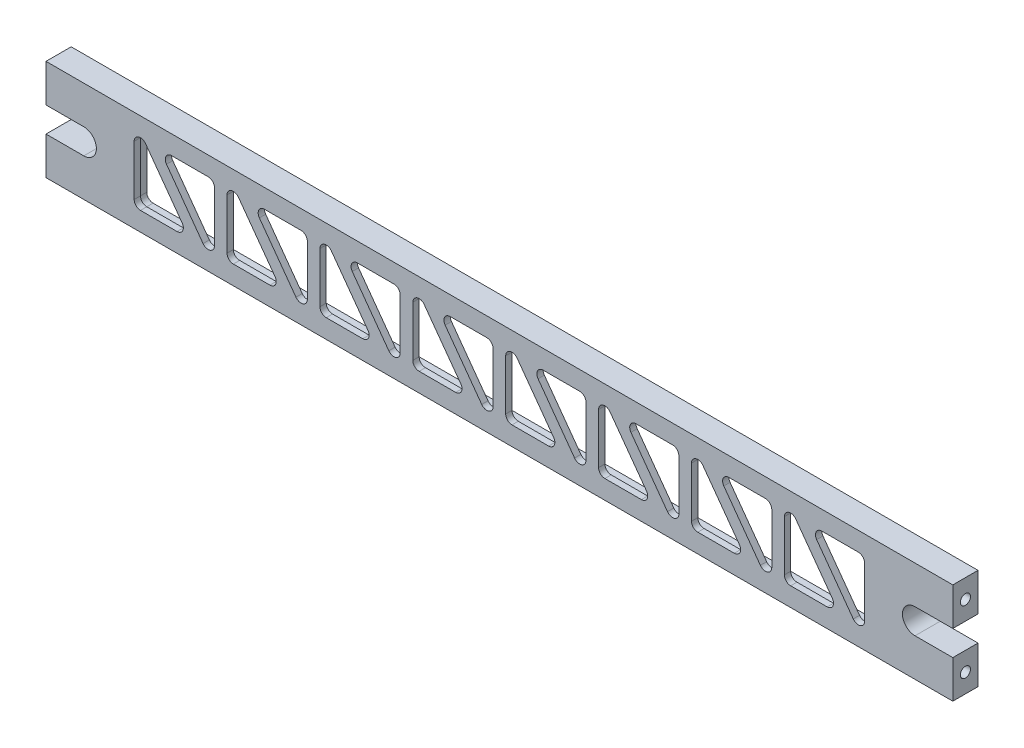
SolidWorks part; units mm, degrees
material "6061 Alloy"
ref_plane "Front Plane" through (0, 0, 0) normal (0, 0, 1) x (1, 0, 0)
ref_plane "Top Plane" through (0, 0, 0) normal (0, 1, 0) x (1, 0, 0)
ref_plane "Right Plane" through (0, 0, 0) normal (1, 0, 0) x (0, 0, -1)
sketch "Sketch1" plane through (0, 0, 0) normal (1, 0, 0) x (0, 0, -1)
  line L1 (0, 0) -> (12.7, 0)
  line L2 (0, 0) -> (0, 50.8)
  line L3 (0, 50.8) -> (12.7, 50.8)
  line L4 (12.7, 0) -> (12.7, 50.8)
  dimension "D1" = 12.7
  dimension "D2" = 50.8
extrude "Boss-Extrude1" add sketch "Sketch1" along normal mid plane 457.2
hole_wizard "1/4-20 Tapped Hole1" positions "3DSketch1" profile "Sketch2" tap size "1/4-20" standard "ANSI Inch"
sketch3d "3DSketch1"
  line L2 (228.6, 9.525, -6.35) -> (228.6, 41.275, -6.35) construction
  line L4 (228.6, 41.275, -6.35) -> (228.6, 50.8, -6.35) construction
  line L5 (228.6, 50.8, -12.7) -> (228.6, 50.8, 0) construction
  line L8 (228.6, 9.525, -6.35) -> (228.6, 0, -6.35) construction
  line L9 (228.6, 0, 0) -> (228.6, 0, -12.7) construction
  point P0 (228.6, 41.275, -6.35)
  point P2 (228.6, 9.525, -6.35)
  point P4 (-228.6, 9.525, -6.35)
  point P6 (-228.6, 41.275, -6.35)
  dimension "D1" = 31.75
sketch "Sketch2" plane through (228.6, 41.275, -6.35) normal (0, 1, 0) x (0, 0, -1)
  line L0 (0, 0) -> (0, 30.7438)
  line L1 (0, 30.7438) -> (2.5527, 29.21)
  line L2 (2.5527, 29.21) -> (2.5527, 0)
  line L5 (2.5527, 0) -> (0, 0)
  line L10 (0, 30.7438) -> (-2.5527, 29.21) construction
  line L11 (0, -6.35) -> (0, 107.95) construction
  dimension "Tap Drill Dia." = 5.1054
  dimension "Tap Drill Depth" = 29.21
  dimension "Drill Angle" = 118
sketch "Sketch4" plane through (0, 0, -12.7) normal (0, 0, -1) x (-1, 0, 0)
  line L0 (0, 0) -> (0, 3.175) construction
  line L1 (187.325, 47.625) -> (-187.325, 47.625)
  line L2 (190.5, 44.45) -> (190.5, 6.35)
  line L3 (187.325, 3.175) -> (-187.325, 3.175)
  line L4 (-190.5, 44.45) -> (-190.5, 6.35)
  line L5 (-228.6, 0) -> (228.6, 0) construction
  line L6 (0, 47.625) -> (0, 50.8) construction
  line L7 (-228.6, 50.8) -> (228.6, 50.8) construction
  line L8 (228.6, 25.4) -> (190.5, 25.4) construction
  line L9 (228.6, 0) -> (228.6, 50.8) construction
  line L10 (-228.6, 25.4) -> (-190.5, 25.4) construction
  line L11 (-228.6, 0) -> (-228.6, 50.8) construction
  arc A0 (-187.325, 3.175) -> (-190.5, 6.35) centre (-187.325, 6.35) cw
  arc A1 (-187.325, 47.625) -> (-190.5, 44.45) centre (-187.325, 44.45) ccw
  arc A2 (190.5, 6.35) -> (187.325, 3.175) centre (187.325, 6.35) cw
  arc A3 (187.325, 47.625) -> (190.5, 44.45) centre (187.325, 44.45) cw
  dimension "D1" = 3.175
  dimension "D2" = 3.175
  dimension "D3" = 38.1
extrude "Cut-Extrude1" cut sketch "Sketch4" against normal blind 9.525
sketch "Sketch5" plane through (0, 0, -3.175) normal (0, 0, -1) x (-1, 0, 0)
  line L0 (-184.15, 38.1) -> (-184.15, 12.7)
  line L1 (-178.4056, 10.8349) -> (-159.9676, 36.2349)
  line L2 (-162.537, 41.275) -> (-180.975, 41.275)
  line L3 (-167.8511, 14.5651) -> (-149.4132, 39.9651)
  line L4 (-143.6687, 38.1) -> (-143.6687, 12.7)
  line L5 (-146.8438, 9.525) -> (-165.2817, 9.525)
  line L6 (187.325, 47.625) -> (-187.325, 47.625) construction
  line L7 (-187.325, 3.175) -> (187.325, 3.175) construction
  line L8 (-190.5, 25.4) -> (-184.15, 25.4) construction
  line L9 (-190.5, 44.45) -> (-190.5, 6.35) construction
  line L10 (-169.1866, 23.5349) -> (-164.0478, 19.8046) construction
  line L11 (-143.6688, 25.4) -> (-137.3188, 25.4) construction
  line L12 (-137.3188, 38.1) -> (-137.3188, 12.7)
  line L13 (-115.7058, 41.275) -> (-134.1438, 41.275)
  line L14 (-131.5743, 10.8349) -> (-113.1364, 36.2349)
  line L15 (-122.3554, 23.5349) -> (-117.2165, 19.8046) construction
  line L16 (-121.0199, 14.5651) -> (-102.5819, 39.9651)
  line L17 (-96.8375, 38.1) -> (-96.8375, 12.7)
  line L18 (-100.0125, 9.525) -> (-118.4505, 9.525)
  line L19 (-96.8375, 25.4) -> (-90.4875, 25.4) construction
  line L20 (-90.4875, 38.1) -> (-90.4875, 12.7)
  line L21 (-68.8745, 41.275) -> (-87.3125, 41.275)
  line L22 (-84.7431, 10.8349) -> (-66.3051, 36.2349)
  line L23 (-75.5241, 23.5349) -> (-70.3853, 19.8046) construction
  line L24 (-74.1886, 14.5651) -> (-55.7507, 39.9651)
  line L25 (-50.0062, 38.1) -> (-50.0062, 12.7)
  line L26 (-53.1812, 9.525) -> (-71.6192, 9.525)
  line L27 (-50.0063, 25.4) -> (-43.6563, 25.4) construction
  line L28 (-43.6563, 38.1) -> (-43.6563, 12.7)
  line L29 (-22.0433, 41.275) -> (-40.4812, 41.275)
  line L30 (-37.9118, 10.8349) -> (-19.4739, 36.2349)
  line L31 (-28.6929, 23.5349) -> (-23.554, 19.8046) construction
  line L32 (-27.3574, 14.5651) -> (-8.9194, 39.9651)
  line L33 (-3.175, 38.1) -> (-3.175, 12.7)
  line L34 (-6.35, 9.525) -> (-24.788, 9.525)
  line L35 (-3.175, 25.4) -> (3.175, 25.4) construction
  line L36 (3.175, 38.1) -> (3.175, 12.7)
  line L37 (24.788, 41.275) -> (6.35, 41.275)
  line L38 (8.9194, 10.8349) -> (27.3574, 36.2349)
  line L39 (18.1384, 23.5349) -> (23.2772, 19.8046) construction
  line L40 (19.4739, 14.5651) -> (37.9118, 39.9651)
  line L41 (43.6563, 38.1) -> (43.6563, 12.7)
  line L42 (40.4812, 9.525) -> (22.0433, 9.525)
  line L43 (43.6562, 25.4) -> (50.0062, 25.4) construction
  line L44 (50.0062, 38.1) -> (50.0062, 12.7)
  line L45 (71.6192, 41.275) -> (53.1812, 41.275)
  line L46 (55.7507, 10.8349) -> (74.1886, 36.2349)
  line L47 (64.9696, 23.5349) -> (70.1085, 19.8046) construction
  line L48 (66.3051, 14.5651) -> (84.7431, 39.9651)
  line L49 (90.4875, 38.1) -> (90.4875, 12.7)
  line L50 (87.3125, 9.525) -> (68.8745, 9.525)
  line L51 (90.4875, 25.4) -> (96.8375, 25.4) construction
  line L52 (96.8375, 38.1) -> (96.8375, 12.7)
  line L53 (118.4505, 41.275) -> (100.0125, 41.275)
  line L54 (102.5819, 10.8349) -> (121.0199, 36.2349)
  line L55 (111.8009, 23.5349) -> (116.9397, 19.8046) construction
  line L56 (113.1364, 14.5651) -> (131.5743, 39.9651)
  line L57 (137.3188, 38.1) -> (137.3188, 12.7)
  line L58 (134.1438, 9.525) -> (115.7058, 9.525)
  line L59 (137.3187, 25.4) -> (143.6687, 25.4) construction
  line L60 (143.6687, 38.1) -> (143.6687, 12.7)
  line L61 (165.2817, 41.275) -> (146.8438, 41.275)
  line L62 (149.4132, 10.8349) -> (167.8511, 36.2349)
  line L63 (158.6321, 23.5349) -> (163.771, 19.8046) construction
  line L64 (159.9676, 14.5651) -> (178.4056, 39.9651)
  line L65 (184.15, 38.1) -> (184.15, 12.7)
  line L66 (180.975, 9.525) -> (162.537, 9.525)
  line L67 (190.5, 25.4) -> (184.15, 25.4) construction
  line L69 (190.5, 6.35) -> (190.5, 44.45) construction
  arc A0 (-167.8511, 14.5651) -> (-165.2817, 9.525) centre (-165.2817, 12.7) ccw
  arc A1 (-143.6687, 12.7) -> (-146.8438, 9.525) centre (-146.8438, 12.7) cw
  arc A2 (-149.4132, 39.9651) -> (-143.6687, 38.1) centre (-146.8438, 38.1) cw
  arc A3 (-159.9676, 36.2349) -> (-162.537, 41.275) centre (-162.537, 38.1) ccw
  arc A4 (-184.15, 12.7) -> (-178.4056, 10.8349) centre (-180.975, 12.7) ccw
  arc A5 (-184.15, 38.1) -> (-180.975, 41.275) centre (-180.975, 38.1) cw
  arc A6 (-137.3188, 38.1) -> (-134.1438, 41.275) centre (-134.1438, 38.1) cw
  arc A7 (-113.1364, 36.2349) -> (-115.7058, 41.275) centre (-115.7058, 38.1) ccw
  arc A8 (-137.3188, 12.7) -> (-131.5743, 10.8349) centre (-134.1438, 12.7) ccw
  arc A9 (-102.5819, 39.9651) -> (-96.8375, 38.1) centre (-100.0125, 38.1) cw
  arc A10 (-96.8375, 12.7) -> (-100.0125, 9.525) centre (-100.0125, 12.7) cw
  arc A11 (-121.0199, 14.5651) -> (-118.4505, 9.525) centre (-118.4505, 12.7) ccw
  arc A12 (-90.4875, 38.1) -> (-87.3125, 41.275) centre (-87.3125, 38.1) cw
  arc A13 (-66.3051, 36.2349) -> (-68.8745, 41.275) centre (-68.8745, 38.1) ccw
  arc A14 (-90.4875, 12.7) -> (-84.7431, 10.8349) centre (-87.3125, 12.7) ccw
  arc A15 (-55.7507, 39.9651) -> (-50.0062, 38.1) centre (-53.1812, 38.1) cw
  arc A16 (-50.0062, 12.7) -> (-53.1812, 9.525) centre (-53.1812, 12.7) cw
  arc A17 (-74.1886, 14.5651) -> (-71.6192, 9.525) centre (-71.6192, 12.7) ccw
  arc A18 (-43.6563, 38.1) -> (-40.4812, 41.275) centre (-40.4812, 38.1) cw
  arc A19 (-19.4739, 36.2349) -> (-22.0433, 41.275) centre (-22.0433, 38.1) ccw
  arc A20 (-43.6563, 12.7) -> (-37.9118, 10.8349) centre (-40.4812, 12.7) ccw
  arc A21 (-8.9194, 39.9651) -> (-3.175, 38.1) centre (-6.35, 38.1) cw
  arc A22 (-3.175, 12.7) -> (-6.35, 9.525) centre (-6.35, 12.7) cw
  arc A23 (-27.3574, 14.5651) -> (-24.788, 9.525) centre (-24.788, 12.7) ccw
  arc A24 (3.175, 38.1) -> (6.35, 41.275) centre (6.35, 38.1) cw
  arc A25 (27.3574, 36.2349) -> (24.788, 41.275) centre (24.788, 38.1) ccw
  arc A26 (3.175, 12.7) -> (8.9194, 10.8349) centre (6.35, 12.7) ccw
  arc A27 (37.9118, 39.9651) -> (43.6563, 38.1) centre (40.4812, 38.1) cw
  arc A28 (43.6563, 12.7) -> (40.4812, 9.525) centre (40.4812, 12.7) cw
  arc A29 (19.4739, 14.5651) -> (22.0433, 9.525) centre (22.0433, 12.7) ccw
  arc A30 (50.0062, 38.1) -> (53.1812, 41.275) centre (53.1812, 38.1) cw
  arc A31 (74.1886, 36.2349) -> (71.6192, 41.275) centre (71.6192, 38.1) ccw
  arc A32 (50.0062, 12.7) -> (55.7507, 10.8349) centre (53.1812, 12.7) ccw
  arc A33 (84.7431, 39.9651) -> (90.4875, 38.1) centre (87.3125, 38.1) cw
  arc A34 (90.4875, 12.7) -> (87.3125, 9.525) centre (87.3125, 12.7) cw
  arc A35 (66.3051, 14.5651) -> (68.8745, 9.525) centre (68.8745, 12.7) ccw
  arc A36 (96.8375, 38.1) -> (100.0125, 41.275) centre (100.0125, 38.1) cw
  arc A37 (121.0199, 36.2349) -> (118.4505, 41.275) centre (118.4505, 38.1) ccw
  arc A38 (96.8375, 12.7) -> (102.5819, 10.8349) centre (100.0125, 12.7) ccw
  arc A39 (131.5743, 39.9651) -> (137.3188, 38.1) centre (134.1438, 38.1) cw
  arc A40 (137.3188, 12.7) -> (134.1438, 9.525) centre (134.1438, 12.7) cw
  arc A41 (113.1364, 14.5651) -> (115.7058, 9.525) centre (115.7058, 12.7) ccw
  arc A42 (143.6687, 38.1) -> (146.8438, 41.275) centre (146.8438, 38.1) cw
  arc A43 (167.8511, 36.2349) -> (165.2817, 41.275) centre (165.2817, 38.1) ccw
  arc A44 (143.6687, 12.7) -> (149.4132, 10.8349) centre (146.8438, 12.7) ccw
  arc A45 (178.4056, 39.9651) -> (184.15, 38.1) centre (180.975, 38.1) cw
  arc A46 (184.15, 12.7) -> (180.975, 9.525) centre (180.975, 12.7) cw
  arc A47 (159.9676, 14.5651) -> (162.537, 9.525) centre (162.537, 12.7) ccw
  point P18 (-146.8438, 41.275)
  point P19 (-180.975, 9.525)
  dimension "D1" = 3.175
  dimension "D2" = 6.35
  dimension "D3" = 6.35
  dimension "D4" = 6.35
  dimension "D5" = 8
extrude "Cut-Extrude2" cut sketch "Sketch5" against normal through all
sketch "Sketch6" plane through (0, 0, 0) normal (0, 0, 1) x (1, 0, 0)
  line L0 (0, 0) -> (0, 50.8) construction
  line L1 (228.6, 50.8) -> (-228.6, 50.8) construction
  line L2 (-209.55, 31.75) -> (-228.6, 31.75)
  line L3 (-228.6, 50.8) -> (-228.6, 0) construction
  line L4 (-228.6, 31.75) -> (-228.6, 19.05)
  line L5 (-228.6, 19.05) -> (-209.55, 19.05)
  line L6 (228.6, 19.05) -> (209.55, 19.05)
  line L8 (228.6, 31.75) -> (228.6, 19.05)
  line L9 (209.55, 31.75) -> (228.6, 31.75)
  arc A0 (-209.55, 19.05) -> (-209.55, 31.75) centre (-209.55, 25.4) ccw
  arc A1 (209.55, 19.05) -> (209.55, 31.75) centre (209.55, 25.4) cw
  point P8 (-228.6, 25.4)
  point P18 (228.6, 25.4)
  dimension "D1" = 12.7
  dimension "D2" = 19.05
extrude "Cut-Extrude3" cut sketch "Sketch6" against normal through all
